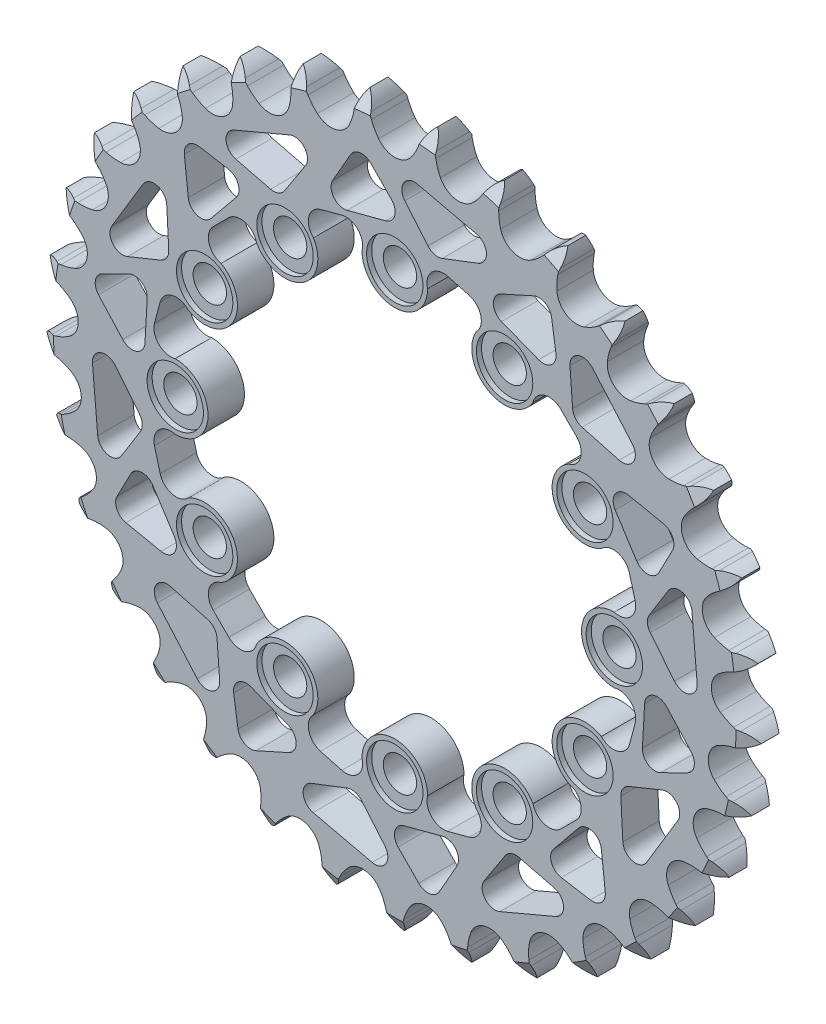
SolidWorks part; units mm, degrees
other "Markup1"
sketch "Sketch15" plane through (70.768, -70.8482, 7.2136) normal (0.2727, -0.0399, 0.9613) x (0.9351, 0.2461, -0.2551)
sketch "Sketch17" plane through (70.768, -70.8482, 7.2136) normal (0.2727, -0.0399, 0.9613) x (0.9351, 0.2461, -0.2551)
sketch "Sketch18" plane through (70.768, -70.8482, 7.2136) normal (0.2727, -0.0399, 0.9613) x (0.9351, 0.2461, -0.2551)
sketch "Sketch19" plane through (70.768, -70.8482, 7.2136) normal (0.2727, -0.0399, 0.9613) x (0.9351, 0.2461, -0.2551)
sketch "Sketch20" plane through (70.768, -70.8482, 7.2136) normal (0.2727, -0.0399, 0.9613) x (0.9351, 0.2461, -0.2551)
sketch "Sketch21" plane through (70.768, -70.8482, 7.2136) normal (0.2727, -0.0399, 0.9613) x (0.9351, 0.2461, -0.2551)
sketch "Sketch22" plane through (70.768, -70.8482, 7.2136) normal (0.2727, -0.0399, 0.9613) x (0.9351, 0.2461, -0.2551)
sketch "Sketch23" plane through (70.768, -70.8482, 7.2136) normal (0.2727, -0.0399, 0.9613) x (0.9351, 0.2461, -0.2551)
material "7075-T6 (SN)"
ref_plane "Front Plane" through (0, 0, 0) normal (0, 0, 1) x (1, 0, 0)
ref_plane "Top Plane" through (0, 0, 0) normal (0, 1, 0) x (1, 0, 0)
ref_plane "Right Plane" through (0, 0, 0) normal (1, 0, 0) x (0, 0, -1)
sketch "Work Sketch" plane through (0, 0, 0) normal (0, 0, 1) x (1, 0, 0)
  line L0 (0, 0) -> (0, 160.4542) construction
  line L1 (-112.0919, 66.8027) -> (87.2579, 66.8027) construction
  line L2 (5.0834, 120.8822) -> (5.0834, 112.9699) construction
  line L3 (-12.8497, 70.6081) -> (16.7256, 70.6081) construction
  line L4 (5.0834, 70.6081) -> (-6.0658, 62.2619) construction
  line L5 (5.0834, 70.6081) -> (-4.6352, 66.9715) construction
  line L6 (-4.6352, 66.9715) -> (-6.998, 73.2861)
  line L7 (-11.5114, 65.7464) -> (-7.1525, 65.7464) construction
  line L8 (-11.0622, 124.7602) -> (-11.0622, 110.2345) construction
  line L9 (0, 0) -> (-4.0639, 42.5596) construction
  circle A0 centre (0, 0) radius 66.8027
  circle A1 centre (0, 66.8027) radius 4.0088
  arc A2 (-4.6352, 66.9715) -> (-3.2092, 64.4003) centre (5.0609, 70.6677) ccw
  circle A3 centre (-11.0622, 65.7464) radius 6.4488
  point P23 (-3.2092, 64.4003)
  dimension "D1" = 133.6054
  dimension "D8" = 10.3767
  dimension "D2" = 8.0177
  dimension "D3" = 5.0834
  dimension "D4" = 3.8054
  dimension "D5" = 36.818
  dimension "D6" = 16.303
  dimension "D7" = 10.3767
  dimension "D9" = 1.0563
  dimension "D10" = 11.0622
  dimension "D11" = 5.455
sketch "Teeth Sketch" plane through (0, 0, 0) normal (0, 0, 1) x (1, 0, 0)
  line L0 (5.0224, 68.0064) -> (4.6352, 66.9715)
  line L1 (-8.8439, 92.6176) -> (-5.6513, 59.1829) construction
  line L2 (0, 0) -> (-12.8498, 132.1321) construction
  line L3 (7.9387, 67.7279) -> (8.123, 66.6385)
  line L4 (19011.2087, -199094.3845) -> (-19015.2726, 199136.9441) construction
  line L5 (0, 146.3285) -> (0, 56.9858) construction
  line L6 (17.8019, 65.8269) -> (17.2258, 64.8841)
  line L7 (0, -200000) -> (0, 200160.4542) construction
  line L8 (20.6128, 65.0016) -> (20.5877, 63.897)
  line L9 (-4.6352, 66.9715) -> (-6.998, 73.2861) construction
  line L10 (43.2949, 52.6844) -> (42.861, 51.6682)
  line L11 (-5.0224, 68.0064) -> (-4.6352, 66.9715)
  line L12 (29.938, 61.2683) -> (29.1939, 60.4515)
  line L13 (32.5419, 59.9259) -> (32.3082, 58.846)
  line L14 (40.9921, 54.4953) -> (40.1069, 53.8341)
  line L15 (50.5647, 45.7527) -> (49.5703, 45.271)
  line L16 (52.4831, 43.5387) -> (51.8648, 42.623)
  line L17 (58.3096, 35.3565) -> (57.2421, 35.0716)
  line L18 (59.7744, 32.8194) -> (58.9939, 32.0373)
  line L19 (63.9472, 23.6824) -> (62.845, 23.6047)
  line L20 (64.9053, 20.9139) -> (63.9909, 20.2936)
  line L21 (67.2735, 11.1523) -> (66.1765, 11.2846)
  line L22 (67.6904, 8.2526) -> (66.6751, 7.8165)
  line L23 (68.1683, -1.7808) -> (67.1162, -1.4433)
  line L24 (68.0289, -4.7071) -> (66.9495, -4.9431)
  line L25 (66.5994, -14.6496) -> (65.6302, -14.119)
  line L26 (65.9088, -17.4966) -> (64.8042, -17.524)
  line L27 (62.6234, -26.9889) -> (61.7722, -26.2845)
  line L28 (61.4065, -29.6537) -> (60.3166, -29.4716)
  line L29 (56.3841, -38.3527) -> (55.6815, -37.4999)
  line L30 (54.6848, -40.739) -> (53.6491, -40.354)
  line L31 (48.1068, -48.3304) -> (47.5783, -47.3601)
  line L32 (45.9866, -50.352) -> (45.0425, -49.7779)
  line L33 (38.0909, -56.5613) -> (37.7556, -55.5085)
  line L34 (35.6264, -58.1451) -> (34.808, -57.4027)
  line L35 (26.6983, -62.7479) -> (26.5682, -61.6506)
  line L36 (23.9786, -63.8367) -> (23.3155, -62.9529)
  line L37 (14.3407, -66.6666) -> (14.4207, -65.5646)
  line L38 (11.4641, -67.221) -> (10.9802, -66.2277)
  line L39 (1.4648, -68.1759) -> (1.7519, -67.1089)
  line L40 (-1.4648, -68.1759) -> (-1.7519, -67.1089)
  line L41 (-11.4641, -67.221) -> (-10.9802, -66.2277)
  line L42 (-14.3407, -66.6666) -> (-14.4207, -65.5646)
  line L43 (-23.9786, -63.8367) -> (-23.3155, -62.9529)
  line L44 (-26.6983, -62.7479) -> (-26.5682, -61.6506)
  line L45 (-35.6264, -58.1451) -> (-34.808, -57.4027)
  line L46 (-38.0909, -56.5613) -> (-37.7556, -55.5085)
  line L47 (-45.9866, -50.352) -> (-45.0425, -49.7779)
  line L48 (-48.1068, -48.3304) -> (-47.5783, -47.3601)
  line L49 (-54.6848, -40.739) -> (-53.6491, -40.354)
  line L50 (-56.3841, -38.3527) -> (-55.6815, -37.4999)
  line L51 (-61.4065, -29.6537) -> (-60.3166, -29.4716)
  line L52 (-62.6234, -26.9889) -> (-61.7722, -26.2845)
  line L53 (-65.9088, -17.4966) -> (-64.8042, -17.524)
  line L54 (-66.5994, -14.6496) -> (-65.6302, -14.119)
  line L55 (-68.0289, -4.7071) -> (-66.9495, -4.9431)
  line L56 (-68.1683, -1.7808) -> (-67.1162, -1.4433)
  line L57 (-67.6904, 8.2526) -> (-66.6751, 7.8165)
  line L58 (-67.2735, 11.1523) -> (-66.1765, 11.2846)
  line L59 (-64.9053, 20.9139) -> (-63.9909, 20.2936)
  line L60 (-63.9472, 23.6824) -> (-62.845, 23.6047)
  line L61 (-59.7744, 32.8194) -> (-58.9939, 32.0373)
  line L62 (-58.3096, 35.3565) -> (-57.2421, 35.0716)
  line L63 (-52.4831, 43.5387) -> (-51.8648, 42.623)
  line L64 (-50.5647, 45.7527) -> (-49.5703, 45.271)
  line L65 (-43.2949, 52.6844) -> (-42.861, 51.6682)
  line L66 (-40.9921, 54.4953) -> (-40.1069, 53.8341)
  line L67 (-32.5419, 59.9259) -> (-32.3082, 58.846)
  line L68 (-29.938, 61.2683) -> (-29.1939, 60.4515)
  line L69 (-20.6128, 65.0016) -> (-20.5877, 63.897)
  line L70 (-17.8019, 65.8269) -> (-17.2258, 64.8841)
  line L71 (-7.9387, 67.7279) -> (-8.123, 66.6385)
  arc A0 (-6.8704, 70.647) -> (-5.0224, 68.0064) centre (-11.0622, 65.7464) cw
  circle A1 centre (-11.0622, 65.7464) radius 6.4488 construction
  arc A2 (-3.2092, 64.4003) -> (-4.6352, 66.9715) centre (5.0609, 70.6677) cw
  arc A3 (-4.6352, 66.9715) -> (-3.2092, 64.4003) centre (5.0609, 70.6677) ccw construction
  circle A4 centre (0, 66.8027) radius 4.0088 construction
  arc A5 (-3.2092, 64.4003) -> (3.2092, 64.4003) centre (0, 66.8027) ccw
  arc A6 (3.2092, 64.4003) -> (4.6352, 66.9715) centre (-5.0609, 70.6677) ccw
  arc A7 (6.8704, 70.647) -> (5.0224, 68.0064) centre (11.0622, 65.7464) ccw
  arc A8 (6.6238, 70.6705) -> (7.9387, 67.7279) centre (1.5803, 66.6518) cw
  arc A9 (9.0366, 63.8438) -> (8.123, 66.6385) centre (18.3434, 68.4328) cw
  arc A10 (9.0366, 63.8438) -> (15.3391, 62.6291) centre (12.6425, 65.5955) ccw
  arc A11 (15.3391, 62.6291) -> (17.2258, 64.8841) centre (8.4044, 70.3484) ccw
  arc A12 (20.1163, 68.0701) -> (17.8019, 65.8269) centre (23.3049, 62.4647) ccw
  arc A13 (19.8786, 68.1399) -> (20.6128, 65.0016) centre (14.1657, 65.1482) cw
  arc A14 (20.9558, 60.9799) -> (20.5877, 63.897) centre (30.9629, 63.7246) cw
  arc A15 (20.9558, 60.9799) -> (26.9145, 58.5944) centre (24.8281, 62.0175) ccw
  arc A16 (26.9145, 58.5944) -> (29.1939, 60.4515) centre (21.5661, 67.4865) ccw
  arc A17 (32.6351, 63.0329) -> (29.938, 61.2683) centre (34.7052, 56.9254) ccw
  arc A18 (32.4149, 63.1465) -> (32.5419, 59.9259) centre (26.2391, 61.29) cw
  arc A19 (32.1176, 55.912) -> (32.3082, 58.846) centre (42.4634, 56.7133) cw
  arc A20 (32.1176, 55.912) -> (37.5172, 52.4419) centre (36.1163, 56.198) ccw
  arc A21 (37.5172, 52.4419) -> (40.1069, 53.8341) centre (33.9483, 62.1856) ccw
  arc A22 (43.9744, 55.7176) -> (40.9921, 54.4953) centre (44.8513, 49.3287) ccw
  arc A23 (43.7796, 55.8708) -> (43.2949, 52.6844) centre (37.3641, 55.2167) cw
  arc A24 (42.1187, 48.8233) -> (42.861, 51.6682) centre (52.429, 47.6521) cw
  arc A25 (42.1187, 48.8233) -> (46.7639, 44.3941) centre (46.0991, 48.3474) ccw
  arc A26 (46.7639, 44.3941) -> (49.5703, 45.271) centre (45.1035, 54.637) ccw
  arc A27 (53.7244, 46.3885) -> (50.5647, 45.7527) centre (53.3763, 39.9491) ccw
  arc A28 (53.5621, 46.5757) -> (52.4831, 43.5387) centre (47.1387, 47.1476) cw
  arc A29 (50.5974, 39.97) -> (51.8648, 42.623) centre (60.4998, 36.8687) cw
  arc A30 (50.5974, 39.97) -> (54.3205, 34.7417) centre (54.4159, 38.7494) ccw
  arc A31 (54.3205, 34.7417) -> (57.2421, 35.0716) centre (54.6285, 45.1138) ccw
  arc A32 (61.5326, 35.3828) -> (58.3096, 35.3565) centre (59.9721, 29.1257) ccw
  arc A33 (61.4087, 35.5974) -> (59.7744, 32.8194) centre (55.2096, 37.3746) cw
  arc A34 (57.2474, 29.6721) -> (58.9939, 32.0373) centre (66.384, 24.7528) cw
  arc A35 (57.2474, 29.6721) -> (59.9137, 23.8336) centre (60.7659, 27.7508) ccw
  arc A36 (59.9137, 23.8336) -> (62.845, 23.6047) centre (62.1792, 33.96) ccw
  arc A37 (67.1168, 23.0983) -> (63.9472, 23.6824) centre (64.4004, 17.2495) ccw
  arc A38 (67.0358, 23.3324) -> (64.9053, 20.9139) centre (61.2851, 26.2507) cw
  arc A39 (61.8283, 18.3017) -> (63.9909, 20.2936) centre (69.8688, 11.7422) cw
  arc A40 (61.8283, 18.3017) -> (63.3416, 12.0642) centre (64.9196, 15.7493) ccw
  arc A41 (63.3416, 12.0642) -> (66.1765, 11.2846) centre (67.4825, 21.5788) ccw
  arc A42 (70.2753, 9.9789) -> (67.2735, 11.1523) centre (66.5011, 4.7499) ccw
  arc A43 (70.2401, 10.2242) -> (67.6904, 8.2526) centre (65.1456, 14.178) cw
  arc A44 (64.1746, 6.2699) -> (66.6751, 7.8165) centre (70.8284, -1.6927) cw
  arc A45 (64.1746, 6.2699) -> (64.48, -0.1413) centre (66.727, 3.1786) ccw
  arc A46 (64.48, -0.1413) -> (67.1162, -1.4433) centre (70.3468, 8.4177) ccw
  arc A47 (70.8939, -3.5011) -> (68.1683, -1.7808) centre (66.1983, -7.9213) ccw
  arc A48 (70.9057, -3.2536) -> (68.0289, -4.7071) centre (66.6515, 1.5929) cw
  arc A49 (64.2015, -5.9885) -> (66.9495, -4.9431) centre (69.2281, -15.0665) cw
  arc A50 (64.2015, -5.9885) -> (63.2881, -12.3417) centre (66.1227, -9.507) ccw
  arc A51 (63.2881, -12.3417) -> (65.6302, -14.119) centre (70.6686, -5.0476) ccw
  arc A52 (68.9501, -16.8546) -> (66.5994, -14.6496) centre (63.5029, -20.3063) ccw
  arc A53 (69.0085, -16.6138) -> (65.9088, -17.4966) centre (65.7485, -11.0498) cw
  arc A54 (61.908, -18.0305) -> (64.8042, -17.524) centre (65.1257, -27.8957) cw
  arc A55 (61.908, -18.0305) -> (59.8087, -24.096) centre (63.1286, -21.849) ccw
  arc A56 (59.8087, -24.096) -> (61.7722, -26.2845) centre (68.4363, -18.3305) ccw
  arc A57 (64.5144, -29.5989) -> (62.6234, -26.9889) centre (58.5123, -31.9573) ccw
  arc A58 (64.6173, -29.3735) -> (61.4065, -29.6537) centre (62.4691, -23.2931) cw
  arc A59 (57.3769, -29.4209) -> (60.3166, -29.4716) centre (58.6695, -39.7167) cw
  arc A60 (57.3769, -29.4209) -> (54.1677, -34.9794) centre (57.8528, -33.4013) ccw
  arc A61 (54.1677, -34.9794) -> (55.6815, -37.4999) centre (63.7305, -30.9509) ccw
  arc A62 (57.7469, -41.2734) -> (56.3841, -38.3527) centre (51.4069, -42.4533) ccw
  arc A63 (57.8906, -41.0716) -> (54.6848, -40.739) centre (56.932, -34.6945) cw
  arc A64 (50.7721, -39.7478) -> (53.6491, -40.354) centre (50.0928, -50.1023) cw
  arc A65 (50.7721, -39.7478) -> (46.5689, -44.5986) centre (50.4861, -43.7465) ccw
  arc A66 (46.5689, -44.5986) -> (47.5783, -47.3601) centre (56.7213, -42.4527) ccw
  arc A67 (48.8923, -51.4562) -> (48.1068, -48.3304) centre (42.4436, -51.415) ccw
  arc A68 (49.0716, -51.2853) -> (45.9866, -50.352) centre (49.3372, -44.842) cw
  arc A69 (42.3322, -48.6382) -> (45.0425, -49.7779) centre (39.7057, -58.677) cw
  arc A70 (42.3322, -48.6382) -> (37.287, -52.6059) centre (41.2947, -52.5105) ccw
  arc A71 (37.287, -52.6059) -> (37.7556, -55.5085) centre (47.662, -52.4201) ccw
  arc A72 (38.2706, -59.7793) -> (38.0909, -56.5613) centre (31.9463, -58.5183) ccw
  arc A73 (38.479, -59.6453) -> (35.6264, -58.1451) centre (39.9592, -53.3687) cw
  arc A74 (32.3624, -55.7707) -> (34.808, -57.4027) centre (27.8834, -65.131) cw
  arc A75 (32.3624, -55.7707) -> (26.6574, -58.7118) centre (30.6108, -59.3766) ccw
  arc A76 (26.6574, -58.7118) -> (26.5682, -61.6506) centre (36.8801, -60.4929) ccw
  arc A77 (26.2657, -65.9417) -> (26.6983, -62.7479) centre (20.2943, -63.5067) ccw
  arc A78 (26.4957, -65.8497) -> (23.9786, -63.8367) centre (29.137, -59.9666) cw
  arc A79 (21.2229, -60.8875) -> (23.3155, -62.9529) centre (15.0534, -69.2309) cw
  arc A80 (21.2229, -60.8875) -> (15.0644, -62.6958) centre (18.8205, -64.0967) ccw
  arc A81 (15.0644, -62.6958) -> (14.4207, -65.5646) centre (24.7653, -66.3793) ccw
  arc A82 (13.3114, -69.7209) -> (14.3407, -66.6666) centre (7.9088, -66.1998) ccw
  arc A83 (13.5547, -69.674) -> (11.4641, -67.221) centre (17.2617, -64.3972) cw
  arc A84 (9.3163, -63.8036) -> (10.9802, -66.2277) centre (1.6794, -70.8287) cw
  arc A85 (9.3163, -63.8036) -> (2.9269, -64.4137) centre (6.35, -66.5002) ccw
  arc A86 (2.9269, -64.4137) -> (1.7519, -67.1089) centre (11.7554, -69.8666) ccw
  arc A87 (-0.1239, -70.9802) -> (1.4648, -68.1759) centre (-4.7625, -66.5002) ccw
  arc A88 (0.1239, -70.9802) -> (-1.4648, -68.1759) centre (4.7625, -66.5002) cw
  arc A89 (-2.9269, -64.4137) -> (-1.7519, -67.1089) centre (-11.7554, -69.8666) cw
  arc A90 (-2.9269, -64.4137) -> (-9.3163, -63.8036) centre (-6.35, -66.5002) ccw
  arc A91 (-9.3163, -63.8036) -> (-10.9802, -66.2277) centre (-1.6794, -70.8287) ccw
  arc A92 (-13.5547, -69.674) -> (-11.4641, -67.221) centre (-17.2617, -64.3972) ccw
  arc A93 (-13.3114, -69.7209) -> (-14.3407, -66.6666) centre (-7.9088, -66.1998) cw
  arc A94 (-15.0644, -62.6958) -> (-14.4207, -65.5646) centre (-24.7653, -66.3793) cw
  arc A95 (-15.0644, -62.6958) -> (-21.2229, -60.8875) centre (-18.8205, -64.0967) ccw
  arc A96 (-21.2229, -60.8875) -> (-23.3155, -62.9529) centre (-15.0534, -69.2309) ccw
  arc A97 (-26.4957, -65.8497) -> (-23.9786, -63.8367) centre (-29.137, -59.9666) ccw
  arc A98 (-26.2657, -65.9417) -> (-26.6983, -62.7479) centre (-20.2943, -63.5067) cw
  arc A99 (-26.6574, -58.7118) -> (-26.5682, -61.6506) centre (-36.8801, -60.4929) cw
  arc A100 (-26.6574, -58.7118) -> (-32.3624, -55.7707) centre (-30.6108, -59.3766) ccw
  arc A101 (-32.3624, -55.7707) -> (-34.808, -57.4027) centre (-27.8834, -65.131) ccw
  arc A102 (-38.479, -59.6453) -> (-35.6264, -58.1451) centre (-39.9592, -53.3687) ccw
  arc A103 (-38.2706, -59.7793) -> (-38.0909, -56.5613) centre (-31.9463, -58.5183) cw
  arc A104 (-37.287, -52.6059) -> (-37.7556, -55.5085) centre (-47.662, -52.4201) cw
  arc A105 (-37.287, -52.6059) -> (-42.3322, -48.6382) centre (-41.2947, -52.5105) ccw
  arc A106 (-42.3322, -48.6382) -> (-45.0425, -49.7779) centre (-39.7057, -58.677) ccw
  arc A107 (-49.0716, -51.2853) -> (-45.9866, -50.352) centre (-49.3372, -44.842) ccw
  arc A108 (-48.8923, -51.4562) -> (-48.1068, -48.3304) centre (-42.4436, -51.415) cw
  arc A109 (-46.5689, -44.5986) -> (-47.5783, -47.3601) centre (-56.7213, -42.4527) cw
  arc A110 (-46.5689, -44.5986) -> (-50.7721, -39.7478) centre (-50.4861, -43.7465) ccw
  arc A111 (-50.7721, -39.7478) -> (-53.6491, -40.354) centre (-50.0928, -50.1023) ccw
  arc A112 (-57.8906, -41.0716) -> (-54.6848, -40.739) centre (-56.932, -34.6945) ccw
  arc A113 (-57.7469, -41.2734) -> (-56.3841, -38.3527) centre (-51.4069, -42.4533) cw
  arc A114 (-54.1677, -34.9794) -> (-55.6815, -37.4999) centre (-63.7305, -30.9509) cw
  arc A115 (-54.1677, -34.9794) -> (-57.3769, -29.4209) centre (-57.8528, -33.4013) ccw
  arc A116 (-57.3769, -29.4209) -> (-60.3166, -29.4716) centre (-58.6695, -39.7167) ccw
  arc A117 (-64.6173, -29.3735) -> (-61.4065, -29.6537) centre (-62.4691, -23.2931) ccw
  arc A118 (-64.5144, -29.5989) -> (-62.6234, -26.9889) centre (-58.5123, -31.9573) cw
  arc A119 (-59.8087, -24.096) -> (-61.7722, -26.2845) centre (-68.4363, -18.3305) cw
  arc A120 (-59.8087, -24.096) -> (-61.908, -18.0305) centre (-63.1286, -21.849) ccw
  arc A121 (-61.908, -18.0305) -> (-64.8042, -17.524) centre (-65.1257, -27.8957) ccw
  arc A122 (-69.0085, -16.6138) -> (-65.9088, -17.4966) centre (-65.7485, -11.0498) ccw
  arc A123 (-68.9501, -16.8546) -> (-66.5994, -14.6496) centre (-63.5029, -20.3063) cw
  arc A124 (-63.2881, -12.3417) -> (-65.6302, -14.119) centre (-70.6686, -5.0476) cw
  arc A125 (-63.2881, -12.3417) -> (-64.2015, -5.9885) centre (-66.1227, -9.507) ccw
  arc A126 (-64.2015, -5.9885) -> (-66.9495, -4.9431) centre (-69.2281, -15.0665) ccw
  arc A127 (-70.9057, -3.2536) -> (-68.0289, -4.7071) centre (-66.6515, 1.5929) ccw
  arc A128 (-70.8939, -3.5011) -> (-68.1683, -1.7808) centre (-66.1983, -7.9213) cw
  arc A129 (-64.48, -0.1413) -> (-67.1162, -1.4433) centre (-70.3468, 8.4177) cw
  arc A130 (-64.48, -0.1413) -> (-64.1746, 6.2699) centre (-66.727, 3.1786) ccw
  arc A131 (-64.1746, 6.2699) -> (-66.6751, 7.8165) centre (-70.8284, -1.6927) ccw
  arc A132 (-70.2401, 10.2242) -> (-67.6904, 8.2526) centre (-65.1456, 14.178) ccw
  arc A133 (-70.2753, 9.9789) -> (-67.2735, 11.1523) centre (-66.5011, 4.7499) cw
  arc A134 (-63.3416, 12.0642) -> (-66.1765, 11.2846) centre (-67.4825, 21.5788) cw
  arc A135 (-63.3416, 12.0642) -> (-61.8283, 18.3017) centre (-64.9196, 15.7493) ccw
  arc A136 (-61.8283, 18.3017) -> (-63.9909, 20.2936) centre (-69.8688, 11.7422) ccw
  arc A137 (-67.0358, 23.3324) -> (-64.9053, 20.9139) centre (-61.2851, 26.2507) ccw
  arc A138 (-67.1168, 23.0983) -> (-63.9472, 23.6824) centre (-64.4004, 17.2495) cw
  arc A139 (-59.9137, 23.8336) -> (-62.845, 23.6047) centre (-62.1792, 33.96) cw
  arc A140 (-59.9137, 23.8336) -> (-57.2474, 29.6721) centre (-60.7659, 27.7508) ccw
  arc A141 (-57.2474, 29.6721) -> (-58.9939, 32.0373) centre (-66.384, 24.7528) ccw
  arc A142 (-61.4087, 35.5974) -> (-59.7744, 32.8194) centre (-55.2096, 37.3746) ccw
  arc A143 (-61.5326, 35.3828) -> (-58.3096, 35.3565) centre (-59.9721, 29.1257) cw
  arc A144 (-54.3205, 34.7417) -> (-57.2421, 35.0716) centre (-54.6285, 45.1138) cw
  arc A145 (-54.3205, 34.7417) -> (-50.5974, 39.97) centre (-54.4159, 38.7494) ccw
  arc A146 (-50.5974, 39.97) -> (-51.8648, 42.623) centre (-60.4998, 36.8687) ccw
  arc A147 (-53.5621, 46.5757) -> (-52.4831, 43.5387) centre (-47.1387, 47.1476) ccw
  arc A148 (-53.7244, 46.3885) -> (-50.5647, 45.7527) centre (-53.3763, 39.9491) cw
  arc A149 (-46.7639, 44.3941) -> (-49.5703, 45.271) centre (-45.1035, 54.637) cw
  arc A150 (-46.7639, 44.3941) -> (-42.1187, 48.8233) centre (-46.0991, 48.3474) ccw
  arc A151 (-42.1187, 48.8233) -> (-42.861, 51.6682) centre (-52.429, 47.6521) ccw
  arc A152 (-43.7796, 55.8708) -> (-43.2949, 52.6844) centre (-37.3641, 55.2167) ccw
  arc A153 (-43.9744, 55.7176) -> (-40.9921, 54.4953) centre (-44.8513, 49.3287) cw
  arc A154 (-37.5172, 52.4419) -> (-40.1069, 53.8341) centre (-33.9483, 62.1856) cw
  arc A155 (-37.5172, 52.4419) -> (-32.1176, 55.912) centre (-36.1163, 56.198) ccw
  arc A156 (-32.1176, 55.912) -> (-32.3082, 58.846) centre (-42.4634, 56.7133) ccw
  arc A157 (-32.4149, 63.1465) -> (-32.5419, 59.9259) centre (-26.2391, 61.29) ccw
  arc A158 (-32.6351, 63.0329) -> (-29.938, 61.2683) centre (-34.7052, 56.9254) cw
  arc A159 (-26.9145, 58.5944) -> (-29.1939, 60.4515) centre (-21.5661, 67.4865) cw
  arc A160 (-26.9145, 58.5944) -> (-20.9558, 60.9799) centre (-24.8281, 62.0175) ccw
  arc A161 (-20.9558, 60.9799) -> (-20.5877, 63.897) centre (-30.9629, 63.7246) ccw
  arc A162 (-19.8786, 68.1399) -> (-20.6128, 65.0016) centre (-14.1657, 65.1482) ccw
  arc A163 (-20.1163, 68.0701) -> (-17.8019, 65.8269) centre (-23.3049, 62.4647) cw
  arc A164 (-15.3391, 62.6291) -> (-17.2258, 64.8841) centre (-8.4044, 70.3484) cw
  arc A165 (-15.3391, 62.6291) -> (-9.0366, 63.8438) centre (-12.6425, 65.5955) ccw
  arc A166 (-9.0366, 63.8438) -> (-8.123, 66.6385) centre (-18.3434, 68.4328) ccw
  arc A167 (-6.6238, 70.6705) -> (-7.9387, 67.7279) centre (-1.5803, 66.6518) ccw
  point P77 (0, 0)
  dimension "D1" = 5.455
  dimension "D2" = 5.555
  dimension "D3" = 33
extrude "Extrusion" add sketch "Teeth Sketch" along normal blind 7.2136 contours A0 region at (0, 0, 0)
ref_axis "Axis2" through (0, 0, 38.9715) along (0, 0, -1)
hole_wizard "M6 Clearance Hole1" positions "Sketch6" profile "Sketch7" hole size "M6" standard "ANSI Metric"
sketch "Sketch6" plane through (0, 0, 0) normal (0, 0, -1) x (-1, 0, 0)
  circle A0 centre (0, 0) radius 43.5
  point P0 (0, 43.5)
  dimension "D1" = 87
sketch "Sketch7" plane through (0, 43.5, 0) normal (1, 0, 0) x (0, 1, 0)
  line L0 (0, 0) -> (0, 19.2548)
  line L1 (0, 19.2548) -> (3.3, 17.272)
  line L2 (3.3, 17.272) -> (3.3, 0)
  line L5 (3.3, 0) -> (0, 0)
  line L10 (0, 19.2548) -> (-3.3, 17.272) construction
  line L11 (0, -6.35) -> (0, 107.95) construction
  dimension "Hole Dia." = 6.6
  dimension "Hole Depth" = 17.272
  dimension "Drill Angle" = 118
pattern_circular "CirPattern1" count 12 over 360 about axis through (0, 0, 38.9715) along (0, 0, -1) of "M6 Clearance Hole1"
sketch "Sketch8" plane through (0, 0, 0) normal (0, 0, -1) x (-1, 0, 0)
  circle A0 centre (0, 0) radius 37
  dimension "D1" = 74
extrude "Cut-Extrude1" cut sketch "Sketch8" against normal through all both and the other way through all
ref_plane "Sprocket Center Plane" through (0, 0, 3.6068) normal (0, 0, 1) x (1, 0, 0)
sketch "Pitch Circle" plane through (0, 0, 3.6068) normal (0, 0, -1) x (-1, 0, 0)
  circle A0 centre (0, 0) radius 66.8027 construction
  dimension "D1" = 133.6054
ref_plane "Center Plane" through (0, 0, 3.6068) normal (0, 0, 1) x (1, 0, 0)
ref_axis "Axis1" through (0, 0, 7.2136) along (0, 0, -1)
sketch "Sketch5" plane through (0, 0, 0) normal (1, 0, 0) x (0, 0, -1)
  line L0 (-1.8288, -70.8482) -> (-5.3848, -70.8482)
  line L1 (-7.2136, -51.2753) -> (0, -51.2753) construction
  line L2 (-5.3848, -70.8482) -> (-5.3848, -67.6547)
  line L3 (-5.3848, -67.6547) -> (-7.2136, -67.6547)
  line L4 (-7.2136, -67.6547) -> (-5.3848, -70.8482)
  line L5 (-7.2136, -67.6547) -> (-7.2136, -70.8482)
  line L6 (-7.2136, -70.8482) -> (-5.3848, -70.8482)
  line L8 (-7.2136, -70.8482) -> (0, -70.8482) construction
  dimension "D1" = 3.556
  dimension "D2" = 3.1936
  dimension "D3" = 1.8288
revolve "Cut-Revolve1" cut sketch "Sketch5" angle 360 about axis through (0, 0, 7.2136) along (0, 0, -1) region at (0, -69.7837, 6.604)
mirror "Mirror1" about plane through (0, 0, 3.6068) normal (0, 0, 1) of "Cut-Revolve1"
sketch "Sketch10" plane through (0, 0, 0) normal (0, 0, 1) x (1, 0, 0)
  circle A0 centre (-43.5, 0) radius 5.588
  dimension "D1" = 11.176
extrude "Cut-Extrude2" cut sketch "Sketch10" against normal blind 1.016 from surface starting at face at (-37, 0, 7.2136)
pattern_circular "CirPattern2" count 12 over 360 about axis through (0, 0, 38.9715) along (0, 0, -1) of "Cut-Extrude2"
ref_plane "Half Plane" through (0, 0, 3.6068) normal (0, 0, 1) x (1, 0, 0)
sketch "Motor Shaft Sprocket Dimensions" plane through (0, 0, 3.6068) normal (0, 0, 1) x (1, 0, 0)
  line L0 (0, 0) -> (-177.8, 0)
  line L1 (-177.8, 0) -> (-177.8, 23.6982)
  line L2 (-180.2273, 51.0991) -> (-5.8945, 66.5421)
  line L3 (-187.3193, -2.1104) -> (-23.1174, -62.6753)
  line L4 (-5.8945, 66.5421) -> (0, 0)
  line L5 (0, 0) -> (-23.1174, -62.6753)
  circle A0 centre (-177.8, 23.6982) radius 27.5082
  circle A1 centre (0, 0) radius 66.8027 construction
  dimension "D3" = 55.0164
  dimension "D1" = 177.8
  dimension "D2" = 23.6982
  dimension "D4" = 205.308
sketch "Sketch11" plane through (0, 0, 0) normal (0, 0, 1) x (1, 0, 0)
  line L0 (-167.2094, -55.7997) -> (-36.0913, 46.3337)
  line L1 (-145.9214, -98.8914) -> (14.8674, -56.8186)
  circle A2 centre (-152.1323, -75.1555) radius 24.535
  circle A3 centre (0, 0) radius 58.7316
  dimension "D2" = 117.4631
  dimension "D3" = 49.07
  dimension "D1" = 169.6838
sketch "Sketch12" plane through (0, 0, 7.2136) normal (0, 0, 1) x (1, 0, 0)
  line L0 (0, 43.5) -> (21.75, 37.6721) construction
  line L1 (9.5763, 35.7393) -> (13.8192, 51.5738) construction
  line L2 (10.4871, 47.6264) -> (14.7311, 46.4892) construction
  line L6 (9.6691, 44.4273) -> (13.84, 43.3098) construction
  line L7 (10.4871, 47.6264) -> (14.7311, 46.4892)
  circle A0 centre (21.75, 37.6721) radius 5.588 construction
  circle A1 centre (0, 43.5) radius 5.588 construction
  circle A2 centre (21.75, 37.6721) radius 5.588 construction
  circle A3 centre (0, 43.5) radius 5.588 construction
  circle A4 centre (0, 43.5) radius 6.5 construction
  circle A5 centre (21.75, 37.6721) radius 6.5 construction
  circle A6 centre (0, 0) radius 37 construction
  arc A7 (0, 37) -> (18.5, 32.0429) centre (0, 0) cw
  circle A8 centre (0, 0) radius 37 construction
  arc A9 (10.4871, 47.6264) -> (6.5, 43.5) centre (9.6691, 44.4273) ccw
  arc A10 (14.7311, 46.4892) -> (16.1208, 40.9221) centre (13.84, 43.3098) cw
  arc A20 (0, 37) -> (6.5, 43.5) centre (0, 43.5) ccw
  arc A21 (16.1208, 40.9221) -> (18.5, 32.0429) centre (21.75, 37.6721) ccw
  dimension "D1" = 42.0178
  dimension "D2" = 6.7001
  dimension "D6" = 4.318
  dimension "D7" = 3.302
extrude "Cut-Extrude3" cut sketch "Sketch12" against normal through all contours A21 A7 A20 A9 L7 A10
pattern_circular "CirPattern3" count 12 over 360 about axis through (0, 0, 7.2136) along (0, 0, -1) of "Cut-Extrude3" reverse direction yes
sketch "Sketch13" plane through (0, 0, 7.2136) normal (0, 0, 1) x (1, 0, 0)
  line L0 (-12.295, 52.6993) -> (-8.767, 58.8746)
  line L1 (-4.7487, 59.3936) -> (-0.6568, 55.2241)
  line L2 (-1.8231, 50.9886) -> (-9.4431, 48.983)
  line L3 (1.9797, 56.3209) -> (6.5673, 50.8863)
  line L4 (9.4175, 50.1531) -> (16.5325, 52.881)
  line L5 (16.1956, 57.7273) -> (4.493, 60.434)
  arc A0 (-4.7487, 59.3936) -> (-8.767, 58.8746) centre (-6.5615, 57.6145) ccw
  arc A1 (-9.4431, 48.983) -> (-12.295, 52.6993) centre (-10.0896, 51.4393) cw
  arc A2 (-1.8231, 50.9886) -> (-0.6568, 55.2241) centre (-2.4696, 53.445) ccw
  arc A3 (9.4175, 50.1531) -> (6.5673, 50.8863) centre (8.5082, 52.5247) cw
  arc A4 (4.493, 60.434) -> (1.9797, 56.3209) centre (3.9206, 57.9593) ccw
  arc A5 (16.5325, 52.881) -> (16.1956, 57.7273) centre (15.6232, 55.2526) ccw
  circle A6 centre (0, 0) radius 43.5 construction
  dimension "D13" = 2.54
  dimension "D15" = 7.62
  dimension "D16" = 2.54
  dimension "D1" = 51.4393
  dimension "D2" = 53.445
  dimension "D3" = 57.6145
  dimension "D4" = 10.0896
  dimension "D5" = 2.4696
  dimension "D6" = 6.5615
  dimension "D7" = 3.9206
  dimension "D8" = 8.5082
  dimension "D9" = 15.6232
  dimension "D10" = 52.5247
  dimension "D11" = 55.2526
  dimension "D12" = 57.9593
  dimension "D14" = 7.112
  dimension "D17" = 7.112
extrude "Cut-Extrude4" cut sketch "Sketch13" against normal through all
pattern_circular "CirPattern5" count 10 over 360 about axis through (0, 0, 38.9715) along (0, 0, -1) of "Cut-Extrude4"
sketch "Sketch14" plane through (0, 0, 0) normal (0, 0, 1) x (1, 0, 0)
  circle A0 centre (0, 0) radius 35.56
  dimension "D1" = 71.12
sketch "Sketch16" plane through (0, 0, 0) normal (0, 0, 1) x (1, 0, 0)
  circle A0 centre (0, 0) radius 33.02
  dimension "D1" = 66.04
equation "\"P\"= 0.500'//Chain Pitch"
equation "\"N\"= 33'//Number of Teeth"
equation "\"Dr\"= 5 / 16'//Roller Diameter"
equation "\"Ds\"= 1.0005 * \"Dr\" + 0.003'Seating Curve DIameter"
equation "\"R\"= \"Ds\" / 2"
equation "\"A\"= 35 + 60 / \"N\""
equation "\"B\"= 18 - 56 / \"N\""
equation "\"ac\"= 0.8 * \"Dr\""
equation "\"M\"= 0.8 * \"Dr\" * cos ( 35 + 60 / \"N\" )"
equation "\"T\"= 0.8 * \"Dr\" * sin ( 35 + 60 / \"N\" )"
equation "\"E\"= 1.3025 * \"Dr\" + 0.0015"
equation "\"Chordal Length of Arc xy\"= ( 2.605 * \"Dr\" + 0.003 ) * sin ( 9 - 28 / \"N\" )"
equation "\"yz\"= \"Dr\" * ( 1.4 * sin ( 17 - 64 / \"N\" ) - 0.8 * sin ( 18 - 56 / \"N\" ) )"
equation "\"ab\"= 1.4 * \"Dr\""
equation "\"W\"= 1.4 * \"Dr\" * cos ( 180 / \"N\" )"
equation "\"V\"= 1.4 * \"Dr\" * sin ( 180 / \"N\" )"
equation "\"F\"= \"Dr\" * ( 0.8 * cos ( 18 - 56 / \"N\" ) + 1.4 * cos ( 17 - 64 / \"N\" ) - 1.3025 )"
equation "\"H\"= sqr ( \"F\" ^ 2 - ( 1.4 * \"Dr\" - \"P\" / 2 ) ^ 2 )"
equation "\"S\"= \"P\" / 2 * cos ( 180 / \"N\" ) + \"H\" * sin ( 180 / \"N\" )"
equation "\"PD\"= \"P\" / ( sin ( 180 / \"N\" ) )"
equation "\"D1@Work Sketch\" = \"PD\""
equation "\"D3@Work Sketch\" = \"M\""
equation "\"D4@Work Sketch\" = \"T\""
equation "\"D5@Work Sketch\" = \"A\""
equation "\"D6@Work Sketch\" = \"B\""
equation "\"D7@Work Sketch\" = \"E\""
equation "\"D8@Work Sketch\" = \"E\""
equation "\"D9@Work Sketch\" = \"V\""
equation "\"D10@Work Sketch\" = \"W\""
equation "\"D2@Work Sketch\" = \"R\" * 2"
equation "\"D11@Work Sketch\" = 180 / \"N\""
equation "\"D2@Teeth Sketch\" = 180 / \"N\" + 0.1"
equation "\"D3@Teeth Sketch\" = \"N\""
equation "\"Edge Thickness\"=0.5"
equation "\"D1@Pitch Circle\"=\"PD\""
equation "\"ST\"= 0.284'//Sprocket Thickness"
